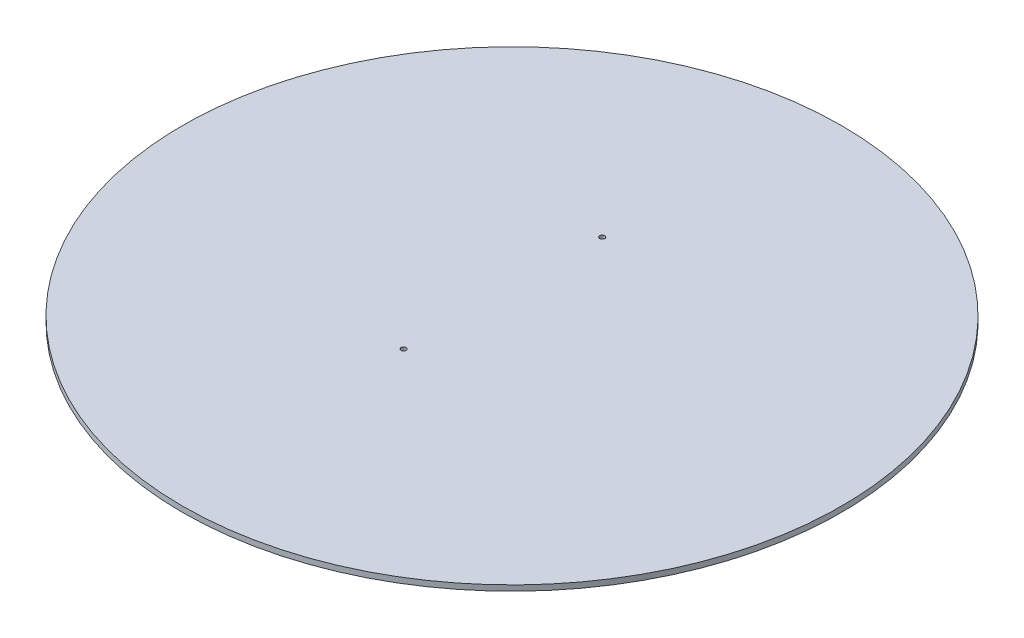
SolidWorks part; units mm, degrees
material "AISI 1020"
ref_plane "Front Plane" through (0, 0, 0) normal (0, 0, 1) x (1, 0, 0)
ref_plane "Top Plane" through (0, 0, 0) normal (0, 1, 0) x (1, 0, 0)
ref_plane "Right Plane" through (0, 0, 0) normal (1, 0, 0) x (0, 0, -1)
sketch "Sketch2" plane through (0, 0, 0) normal (0, 1, 0) x (1, 0, 0)
  circle A0 centre (0, 0) radius 304.8
  dimension "D1" = 609.6
extrude "Boss-Extrude1" add sketch "Sketch2" along normal blind 5.08
extrude "Cut-Extrude1" cut sketch "Sketch3" against normal through all
sketch "Sketch3" plane through (-66.3224, 82.8937, -93.082) normal (0.1079, 0.9936, 0.0319) x (0.9942, -0.108, -0.0006)
  circle A0 centre (50.8264, -172.0317) radius 2.3495
  circle A1 centre (53.1547, 9.3081) radius 2.3495
